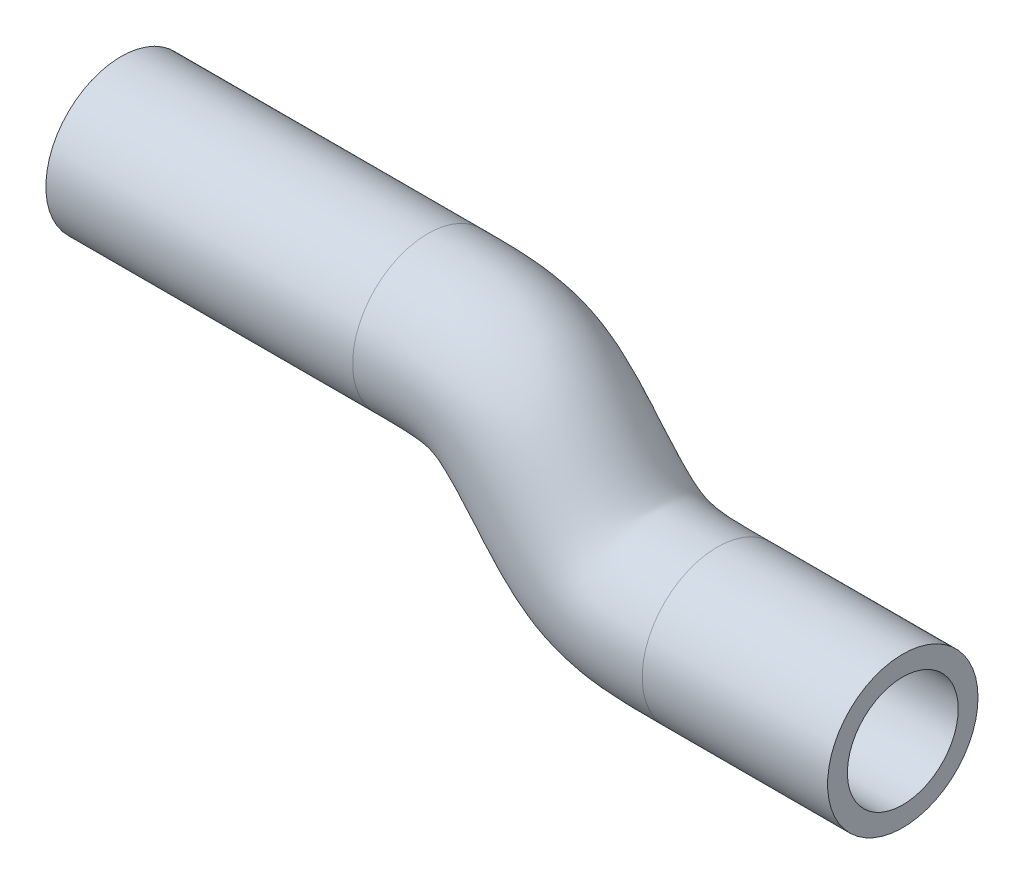
SolidWorks part; units mm, degrees
ref_plane "Front Plane" through (0, 0, 0) normal (0, 0, 1) x (1, 0, 0)
ref_plane "Top Plane" through (0, 0, 0) normal (0, 1, 0) x (1, 0, 0)
ref_plane "Right Plane" through (0, 0, 0) normal (1, 0, 0) x (0, 0, -1)
sketch "Sketch1" plane through (0, 0, 0) normal (0, 0, 1) x (1, 0, 0)
  line L0 (0, 0) -> (39.37, 0)
  line L1 (39.37, 0) -> (39.37, -16.256) construction
  line L2 (39.37, -16.256) -> (76.5302, -16.256) construction
  line L3 (76.5302, -16.256) -> (100.33, -16.256)
  spline S0 degree 3 poles (39.37, 0) (45.0862, 0) (53.1555, -0.2683) (61.9665, -16.4579) (71.0864, -16.256) (76.5302, -16.256) knots 0 0 0 0 0.287251 0.699146 1 1 1 1
  point P7 (51.3947, -2.0859)
  point P9 (63.8933, -14.3345)
  dimension "D1" = 39.37
  dimension "D2" = 16.256
  dimension "D3" = 37.1602
  dimension "D4" = 23.7998
sketch "Sketch2" plane through (0, 0, 0) normal (1, 0, 0) x (0, 0, -1)
  circle A0 centre (0, 0) radius 7.112
  circle A1 centre (0, 0) radius 9.652
  dimension "D1" = 14.224
  dimension "D2" = 2.54
sweep "Sweep1" add profiles "Sketch2" path "Sketch1"
